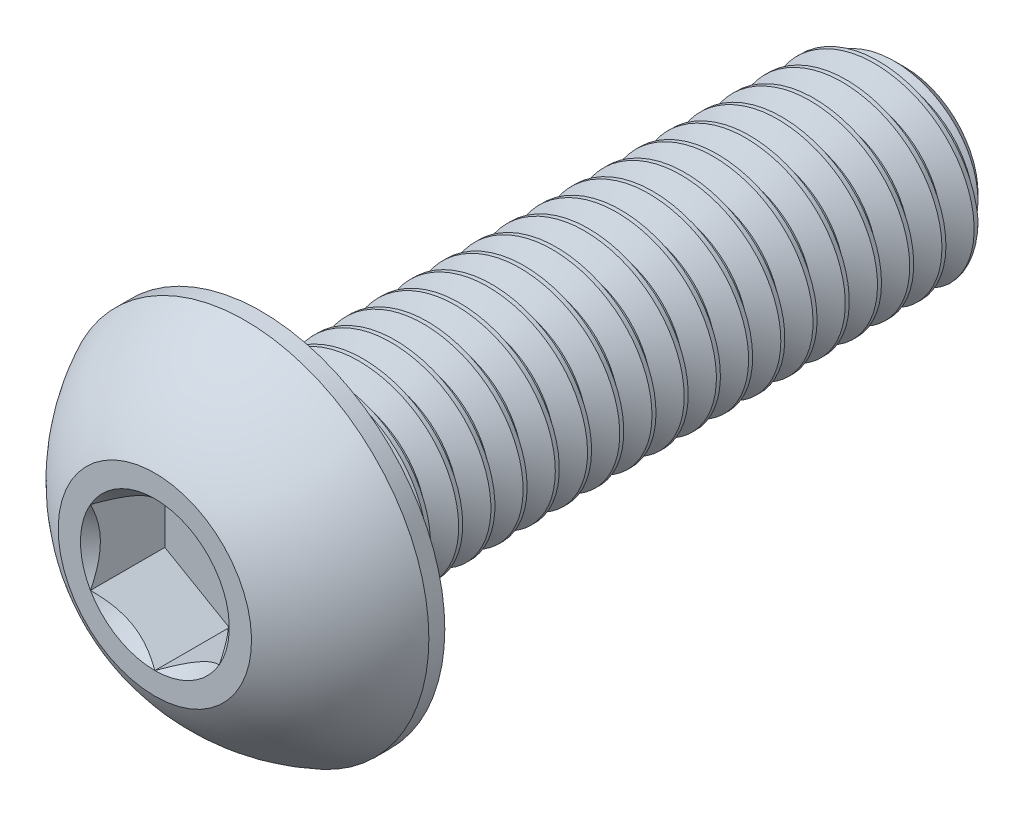
SolidWorks part; units mm, degrees
ref_plane "Front" through (0, 0, 0) normal (0, 0, 1) x (1, 0, 0)
ref_plane "Top" through (0, 0, 0) normal (0, 1, 0) x (1, 0, 0)
ref_plane "Right" through (0, 0, 0) normal (1, 0, 0) x (0, 0, -1)
sketch "Sketch1" plane through (0, 0, 0) normal (1, 0, 0) x (0, 0, -1)
  line L2 (1.65, 1.5) -> (11.65, 1.5)
  line L3 (11.65, 1.5) -> (11.65, 0)
  line L4 (11.65, 0) -> (1.65, 0)
  line L6 (1.4025, 2.85) -> (1.65, 2.85) construction
  line L7 (11.65, 1.5) -> (11.65, -1.5) construction
  line L8 (0, 0) -> (1.65, 0) construction
  line L9 (1.65, 2.85) -> (1.65, -2.85) construction
  line L11 (1.65, 1.5) -> (1.65, 0)
  line L13 (0, 1) -> (0, -1) construction
  line L14 (0, 1) -> (0, 1.5) construction
  arc A3 (0, 1.5) -> (1.4025, 2.85) centre (2.7948, 0) cw construction
  dimension "D1" = 0.2475
  dimension "Head Ht" = 1.65
  dimension "Head Dia" = 5.7
  dimension "Dia" = 3
  dimension "Lg" = 10
  dimension "Hex" = 2
revolve "Revolve1" add sketch "Sketch1" angle 360 mid plane about L4
sketch "Sketch3" plane through (0, 0, -11.65) normal (0, 0, -1) x (-1, 0, 0)
  circle A0 centre (0, 0) radius 1.5
curve "Helix/Spiral1" pitch 0.5 height 10.5 radius 1.5 centre (0, 0, -11.65) axis (0, 0, 1) start towards (0, 1, 0)
sketch "Sketch2" plane through (0, 0, 0) normal (1, 0, 0) x (0, 0, -1)
  line L0 (11.65, 1.5) -> (12.0875, 1.5)
  line L1 (12.0875, 1.5) -> (11.9, 1.1752)
  line L2 (11.9, 1.1752) -> (11.8375, 1.1752)
  line L3 (11.8375, 1.1752) -> (11.65, 1.5)
  line L4 (11.7437, 1.3376) -> (11.9937, 1.3376) construction
  dimension "D1" = 60
  dimension "D2" = 0.0625
  dimension "D3" = 0.25
chamfer "Chamfer1" distance 0.375 angle 45 1 edges at (0, 1.5, -11.65)
sweep "Cut-Sweep1" cut profiles "Sketch2" path "Helix/Spiral1" align with end faces yes
sketch "Sketch7" plane through (0, 0, 0) normal (1, 0, 0) x (0, 0, -1)
  line L6 (1.4025, 2.85) -> (1.65, 2.85) construction
  line L8 (0, 0) -> (1.65, 0) construction
  line L11 (1.65, 2.85) -> (1.65, -2.85) construction
  line L12 (1.4025, 2.85) -> (1.65, 2.85)
  line L13 (0, 0) -> (1.65, 0)
  line L14 (0, 1) -> (0, -1) construction
  line L15 (1.65, 2.85) -> (1.65, 0)
  line L16 (0, 1.5) -> (0, 0)
  arc A2 (1.4025, 2.85) -> (0, 1.5) centre (2.7948, 0) ccw construction
  arc A3 (1.4025, 2.85) -> (0, 1.5) centre (2.7948, 0) ccw
revolve "Revolve2" add sketch "Sketch7" angle 360 mid plane about L13
sketch "Sketch5" plane through (0, 0, 0) normal (0, 0, 1) x (1, 0, 0)
  line L1 (1, -0.5774) -> (1, 0.5774)
  line L2 (1, 0.5774) -> (0, 1.1547)
  line L3 (0, 1.1547) -> (-1, 0.5774)
  line L4 (-1, 0.5774) -> (-1, -0.5774)
  line L5 (-1, -0.5774) -> (0, -1.1547)
  line L6 (0, -1.1547) -> (1, -0.5774)
  circle A0 centre (0, 0) radius 1 construction
extrude "Cut-Extrude2" cut sketch "Sketch5" against normal blind 1.155
sketch "Sketch6" plane through (0, 0, 0) normal (0, 0, 1) x (1, 0, 0)
  circle A0 centre (0, 0) radius 1.1547
extrude "Cut-Extrude3" cut sketch "Sketch6" against normal blind 1.155 draft 45
sketch "Sketch9" [suppressed] plane through (0, 0, -6.6) normal (0, 0, 1) x (1, 0, 0)
  circle A2 centre (0, 0) radius 6
extrude "Boss-Extrude2" [suppressed] add sketch "Sketch9" against normal offset from surface (19 mm away) 32 up to face at (0, 1.125, -11.65)
sketch "Sketch10" plane through (0, 0, 0) normal (1, 0, 0) x (0, 0, -1)
  line L0 (11.65, 1.5) -> (11.65, -1.5) construction
  point P0 (10.9, -1.5)
  dimension "D1" = 0.75
equation "\"D3@Helix/Spiral1\" = \"Lg@Sketch1\" + \"D4@Helix/Spiral1\""
equation "\"D2@Sketch2\" = \"D4@Helix/Spiral1\" * .125"
equation "\"D3@Sketch2\" = \"D4@Helix/Spiral1\" * .5"
equation "\"D1@Chamfer1\" = \"D4@Helix/Spiral1\" * .75"
equation "\"D1@Cut-Extrude2\" = \"Head Ht@Sketch1\" * .7"
equation "\"D1@Sketch1\" = \"Head Ht@Sketch1\" * .15"
equation "\"D1@Sketch10\" = \"D4@Helix/Spiral1\" * 1.5"
equation "\"D1@Cut-Extrude3\" = \"D1@Cut-Extrude2\""
